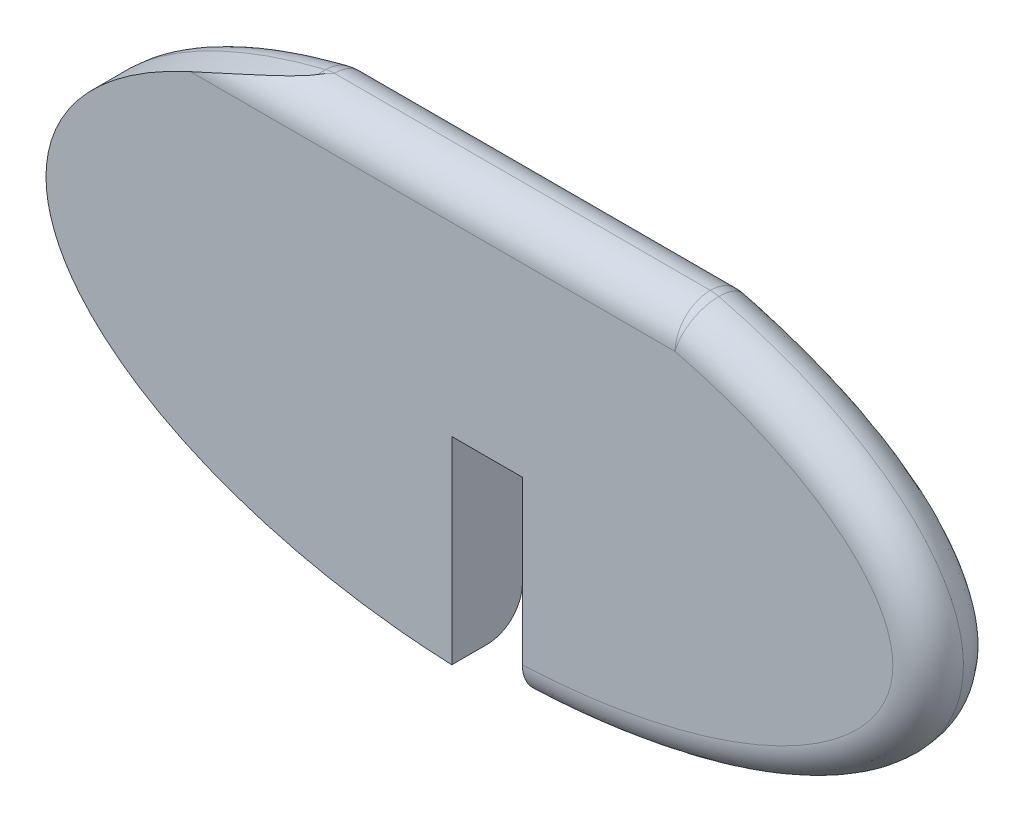
SolidWorks part; units mm, degrees
ref_plane "Front Plane" through (0, 0, 0) normal (0, 0, 1) x (1, 0, 0)
ref_plane "Top Plane" through (0, 0, 0) normal (0, 1, 0) x (1, 0, 0)
ref_plane "Right Plane" through (0, 0, 0) normal (1, 0, 0) x (0, 0, -1)
sketch "Sketch1" plane through (0, 0, 0) normal (0, 0, 1) x (1, 0, 0)
  line L0 (21.7945, 22.5) -> (-21.7945, 22.5)
  ellipse E0 centre (0, 0) end of major axis (-50, 0) minor radius 25 (-21.7945, 22.5) -> (21.7945, 22.5) ccw
  dimension "D1" = 50
  dimension "D2" = 25
  dimension "D3" = 22.5
extrude "Boss-Extrude1" add sketch "Sketch1" along normal mid plane 8
sketch "Sketch2" plane through (0, 0, 4) normal (0, 0, 1) x (1, 0, 0)
  line L0 (21.7945, 22.5) -> (-21.7945, 22.5) construction
  line L1 (-4, -2.5) -> (4, -2.5)
  line L2 (-4, -2.5) -> (-4, -32.5)
  line L3 (-4, -32.5) -> (4, -32.5)
  line L4 (4, -2.5) -> (4, -32.5)
  point P6 (0, -2.5)
  dimension "D1" = 25
  dimension "D2" = 30
  dimension "D3" = 8
extrude "Cut-Extrude1" cut sketch "Sketch2" against normal through all both and the other way through all
fillet "Fillet2" radius 4 7 edges at (49.1425, -4.6102, 4) (0, 22.5, 4) (-49.1425, -4.6102, -4) (-21.7945, 22.5, 0) (21.7945, 22.5, 0) (0, 22.5, -4) (49.1425, -4.6102, -4)
